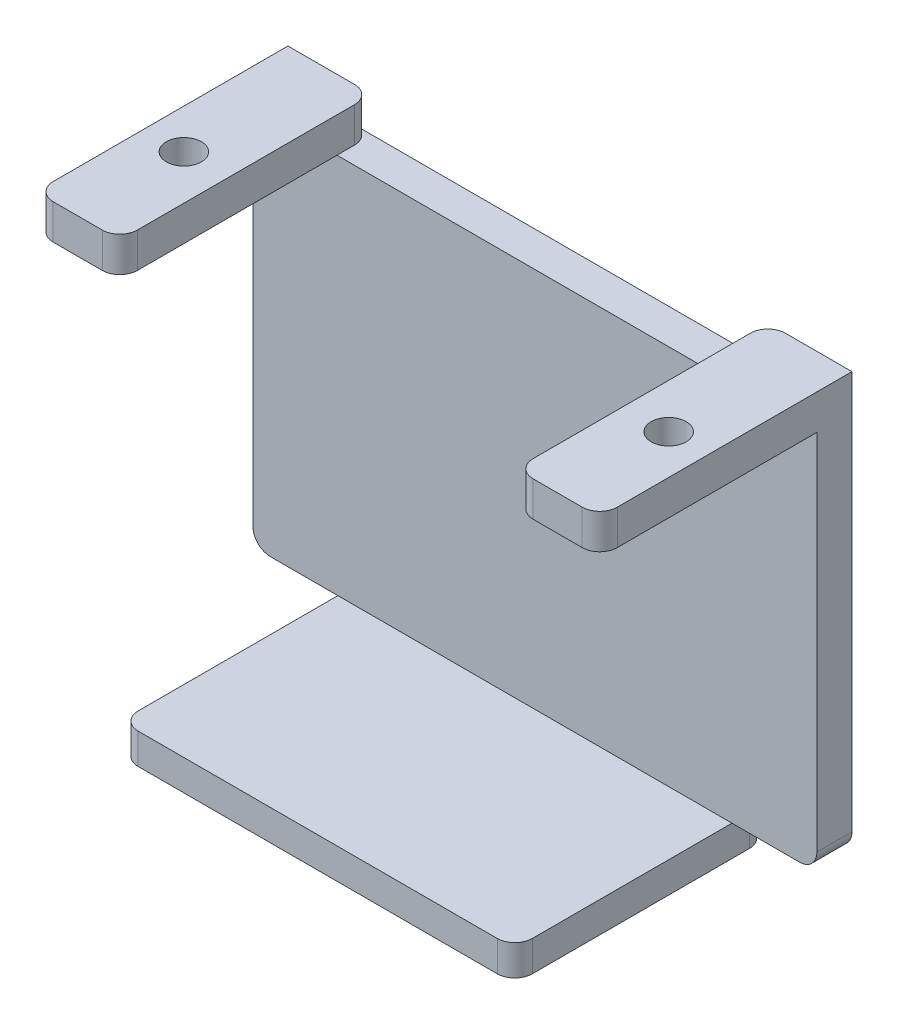
SolidWorks part; units mm, degrees
ref_plane "Front Plane" through (0, 0, 0) normal (0, 0, 1) x (1, 0, 0)
ref_plane "Top Plane" through (0, 0, 0) normal (0, 1, 0) x (1, 0, 0)
ref_plane "Right Plane" through (0, 0, 0) normal (1, 0, 0) x (0, 0, -1)
sketch "Sketch1" plane through (0, 0, 0) normal (0, 0, 1) x (1, 0, 0)
  line L1 (-16.1, 12.75) -> (16.1, 12.75)
  line L2 (-16.1, 12.75) -> (-16.1, -12.75)
  line L3 (-16.1, -12.75) -> (16.1, -12.75)
  line L4 (16.1, 12.75) -> (16.1, -12.75)
  line L5 (-16.1, 12.75) -> (16.1, -12.75) construction
  line L6 (-16.1, -12.75) -> (16.1, 12.75) construction
  point P0 (0, 0)
  dimension "D1" = 32.2
  dimension "D2" = 25.5
extrude "Boss-Extrude1" add sketch "Sketch1" along normal blind 14.4
sketch "Sketch3" plane through (0, 0, 14.4) normal (0, 0, 1) x (1, 0, 0)
  line L0 (-16.1, 12.75) -> (-16.1, -12.75) construction
  line L1 (-16.1, 10.75) -> (16.1, 10.75)
  line L2 (-16.1, 10.75) -> (-16.1, -11)
  line L3 (-16.1, -11) -> (16.1, -11)
  line L4 (16.1, 10.75) -> (16.1, -11)
  line L5 (16.1, -12.75) -> (16.1, 12.75) construction
  line L6 (16.1, 12.75) -> (-16.1, 12.75) construction
  dimension "D1" = 2
  dimension "D2" = 21.75
extrude "Cut-Extrude1" cut sketch "Sketch3" against normal blind 12.4
sketch "Sketch5" plane through (0, 0, 14.4) normal (0, 0, 1) x (1, 0, 0)
  line L0 (16.1, 12.75) -> (-16.1, 12.75) construction
  line L1 (-11.3, 12.75) -> (11.3, 12.75)
  line L2 (-11.3, 12.75) -> (-11.3, 10.75)
  line L3 (-11.3, 10.75) -> (11.3, 10.75)
  line L4 (11.3, 12.75) -> (11.3, 10.75)
  line L5 (16.1, 10.75) -> (-16.1, 10.75) construction
  line L6 (-16.1, 12.75) -> (-16.1, 10.75) construction
  line L7 (16.1, 10.75) -> (16.1, 12.75) construction
  dimension "D1" = 4.8
  dimension "D2" = 4.8
extrude "Cut-Extrude2" cut sketch "Sketch5" against normal blind 14.4 contours L2 L1 L4 L3
fillet "Fillet1" radius 1 1 edges at (-11.3, 11.75, 14.4)
fillet "Fillet2" radius 1 1 edges at (-16.1, 11.75, 14.4)
fillet "Fillet3" radius 1 1 edges at (11.3, 11.75, 14.4)
fillet "Fillet4" radius 1 1 edges at (16.1, 11.75, 14.4)
sketch "Sketch10" plane through (0, 12.75, 0) normal (0, 1, 0) x (1, 0, 0)
  line L0 (-16.1, -13.4) -> (-16.1, 0) construction
  circle A0 centre (-13.84, -8.203) radius 1
  dimension "D1" = 2.26
extrude "Cut-Extrude3" cut sketch "Sketch10" against normal blind 10
mirror "Mirror1" about plane through (0, 0, 0) normal (1, 0, 0) of "Cut-Extrude3"
sketch "Sketch11" plane through (0, 0, 14.4) normal (0, 0, 1) x (1, 0, 0)
  line L0 (-16.1, -12.75) -> (16.1, -12.75) construction
  line L1 (-16.1, -11) -> (-11.25, -11)
  line L2 (-16.1, -11) -> (-16.1, -12.75)
  line L3 (-16.1, -12.75) -> (-11.25, -12.75)
  line L4 (-11.25, -11) -> (-11.25, -12.75)
  dimension "D1" = 4.85
extrude "Cut-Extrude4" cut sketch "Sketch11" against normal blind 20
mirror "Mirror2" about plane through (0, 0, 0) normal (1, 0, 0) of "Cut-Extrude4"
fillet "Fillet5" radius 1 6 edges at (-11.25, -11.875, 0) (-16.1, -11, 1) (16.1, -11, 1) (11.25, -11.875, 0) (11.25, -11.875, 14.4) (-11.25, -11.875, 14.4)
fillet "Fillet6" radius 1 2 edges at (-11.3, 11.75, 0) (11.3, 11.75, 0)
